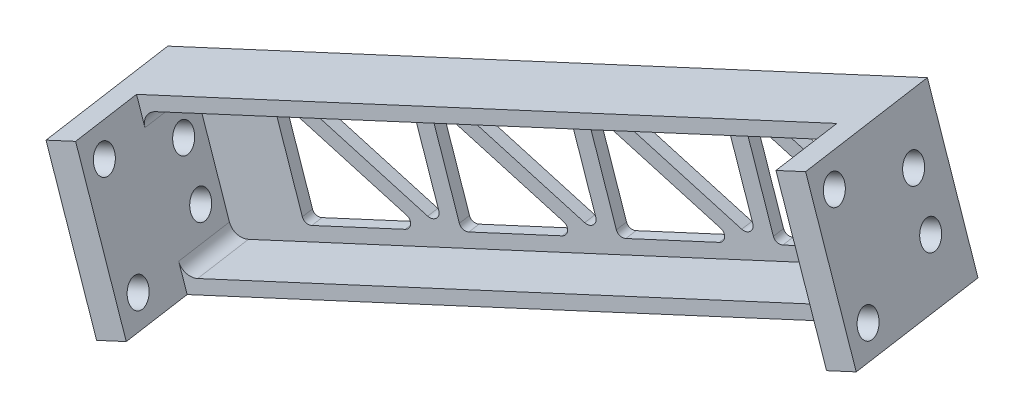
SolidWorks part; units mm, degrees
ref_plane "Front Plane" through (0, 0, 0) normal (0, 0, 1) x (1, 0, 0)
ref_plane "Top Plane" through (0, 0, 0) normal (0, 1, 0) x (1, 0, 0)
ref_plane "Right Plane" through (0, 0, 0) normal (1, 0, 0) x (0, 0, -1)
sketch3d "3DSketch1"
  line L0 (0, 0, 0) -> (-222.8841, -76.2, 50.8) construction
  line L1 (0, 0, 0) -> (-222.8841, 0, 50.8) construction
  line L2 (-222.8841, 0, 50.8) -> (-222.8841, -76.2, 50.8) construction
  line L3 (-222.8841, -76.2, 50.8) -> (-222.8841, -76.2, 0) construction
  line L4 (0, 0, 0) -> (-222.8841, -76.2, 0) construction
  line L5 (-193.5165, -66.1598, 44.1065) -> (-150.59, -51.484, 34.3226)
  line L6 (-150.59, -51.484, 34.3226) -> (0, 0, 0)
  line L7 (-193.5165, -66.1598, 44.1065) -> (-222.8841, -76.2, 50.8)
  dimension "D1" = 228.6
  dimension "D2" = 76.2
  dimension "D3" = 50.8
  dimension "D4" = 31.75
ref_plane "Plane1" through (0, 0, 0) normal (-0.925, -0.3162, 0.2108) x (0.1995, 0.0682, 0.9775)
ref_plane "Plane2" through (-222.8841, -76.2, 50.8) normal (-0.925, -0.3162, 0.2108) x (0.1995, 0.0682, 0.9775)
sketch "Sketch2" plane through (0, 0, 0) normal (-0.925, -0.3162, 0.2108) x (0.1995, 0.0682, 0.9775)
  line L1 (19.05, -19.05) -> (-19.05, -19.05)
  line L2 (19.05, -19.05) -> (19.05, 19.05)
  line L3 (19.05, 19.05) -> (-19.05, 19.05)
  line L4 (-19.05, -19.05) -> (-19.05, 19.05)
  line L5 (19.05, -19.05) -> (-19.05, 19.05) construction
  line L6 (19.05, 19.05) -> (-19.05, -19.05) construction
  point P0 (0, 0)
  dimension "D1" = 38.1
extrude "Boss-Extrude1" add sketch "Sketch2" along normal blind 6.35
sketch "Sketch3" plane through (-5.8735, -2.008, 1.3387) normal (-0.925, -0.3162, 0.2108) x (0.1995, 0.0682, 0.9775)
  line L0 (-15.875, -15.875) -> (0, -15.875)
  line L1 (-19.05, 19.05) -> (0, 19.05)
  line L2 (-19.05, 19.05) -> (-19.05, -19.05)
  line L3 (-19.05, -19.05) -> (0, -19.05)
  line L4 (0, 19.05) -> (0, 15.875)
  line L5 (-19.05, 19.05) -> (0, -19.05) construction
  line L6 (-19.05, -19.05) -> (0, 19.05) construction
  line L7 (-15.875, 15.875) -> (-15.875, -15.875)
  line L8 (-15.875, 15.875) -> (0, 15.875)
  line L9 (0, -15.875) -> (0, -19.05)
  line L10 (-19.05, 19.05) -> (-19.05, -19.05) construction
  line L11 (19.05, 19.05) -> (-19.05, 19.05) construction
  point P0 (-9.525, 0)
  dimension "D1" = 38.1
  dimension "D2" = 19.05
  dimension "D3" = 3.175
extrude "Boss-Extrude2" add sketch "Sketch3" along normal up to vertex (156.4566 mm away) up to point (-150.59, -51.484, 34.3226)
sketch "Sketch4" plane through (-150.59, -51.484, 34.3226) normal (-0.925, -0.3162, 0.2108) x (0.1995, 0.0682, 0.9775)
  line L1 (-19.05, 19.05) -> (19.05, 19.05)
  line L2 (-19.05, 19.05) -> (-19.05, -19.05)
  line L3 (-19.05, -19.05) -> (19.05, -19.05)
  line L4 (19.05, 19.05) -> (19.05, -19.05)
  line L5 (-19.05, 19.05) -> (19.05, -19.05) construction
  line L6 (-19.05, -19.05) -> (19.05, 19.05) construction
  point P0 (0, 0)
  dimension "D1" = 38.1
extrude "Boss-Extrude3" add sketch "Sketch4" against normal blind 6.35
fillet "Fillet1" radius 3.175 4 edges at (-12.5924, 12.472, -6.4204) (-2.3214, -17.5708, -6.4204) (-151.4354, -34.9959, 25.2248) (-141.1643, -65.0386, 25.2248)
hole_wizard "1/4 (0.25) Diameter Hole1" positions "Sketch6" profile "Sketch7" hole size "1/4" standard "ANSI Inch" end condition up to next
sketch "Sketch6" plane through (-144.7165, -49.4759, 32.9839) normal (0.925, 0.3162, -0.2108) x (-0.1995, -0.0682, -0.9775)
  line L0 (0, -19.05) -> (-19.05, -19.05) construction
  line L1 (-19.05, -19.05) -> (-19.05, 19.05) construction
  line L2 (-19.05, 19.05) -> (0, 19.05) construction
  line L3 (15.875, -12.7) -> (15.875, 12.7) construction
  point P0 (9.525, -6.35)
  point P2 (-12.7, -12.7)
  point P4 (-12.7, 12.7)
  point P6 (9.4701, 6.35)
  dimension "D1" = 6.35
  dimension "D2" = 6.35
  dimension "D3" = 6.35
  dimension "D4" = 12.7
  dimension "D5" = 12.7
  dimension "D6" = 6.35
sketch "Sketch7" plane through (-144.5623, -56.1341, 23.673) normal (-0.0803, 0.7048, 0.7048) x (-0.3715, 0.635, -0.6773)
  line L0 (0, 0) -> (0, 25.6035)
  line L1 (0, 25.6035) -> (3.175, 25.6035)
  line L2 (3.175, 25.6035) -> (3.175, 0)
  line L5 (3.175, 0) -> (0, 0)
  line L11 (0, -6.35) -> (0, 107.95) construction
  dimension "Thru Hole Dia." = 6.35
  dimension "Thru Hole Depth" = 25.6035
sketch "Sketch8" plane through (-144.7165, -49.4759, 32.9839) normal (0.925, 0.3162, -0.2108) x (-0.1995, -0.0682, -0.9775)
  circle A0 centre (9.4701, 6.35) radius 5.334 construction
  circle A1 centre (9.525, -6.35) radius 5.334 construction
  circle A2 centre (-12.7, -12.7) radius 5.334 construction
  circle A3 centre (-12.7, 12.7) radius 5.334 construction
  dimension "D1" = 10.668
ref_plane "Plane3" through (-75.295, -25.742, 17.1613) normal (0.925, 0.3162, -0.2108) x (-0.1995, -0.0682, -0.9775)
mirror "Mirror1" about plane through (-75.295, -25.742, 17.1613) normal (0.925, 0.3162, -0.2108) of "1/4 (0.25) Diameter Hole1"
sketch "Sketch9" plane through (-3.1668, -1.0827, -15.5182) normal (0.1995, 0.0682, 0.9775) x (0.9799, -0.0139, -0.199)
  line L0 (-6.0635, -11.5148) -> (-12.6596, 7.3449)
  line L1 (-14.6822, 8.3194) -> (-33.5419, 1.7233)
  line L2 (-33.7068, -1.2054) -> (-8.251, -13.4691)
  line L3 (-149.9286, -35.6184) -> (-14.2318, 11.8404) construction
  line L4 (6.289, -17.9819) -> (-6.289, 17.9819) construction
  line L5 (-149.9286, -35.6184) -> (-14.2318, 11.8404) construction
  line L6 (0.2951, -20.0783) -> (-12.283, 15.8856) construction
  line L7 (-37.9452, -2.6877) -> (-12.4894, -14.9514)
  line L8 (-12.6544, -17.8801) -> (-31.5141, -24.4761)
  line L9 (-33.5367, -23.5017) -> (-40.1327, -4.642)
  line L10 (-139.4469, -65.5884) -> (-3.7501, -18.1295) construction
  line L11 (-8.6204, -4.2041) -> (-36.8347, -14.0719) construction
  arc A0 (-33.5419, 1.7233) -> (-33.7068, -1.2054) centre (-33.0178, 0.2248) ccw
  arc A1 (-12.6596, 7.3449) -> (-14.6822, 8.3194) centre (-14.1581, 6.8209) ccw
  arc A2 (-6.0635, -11.5148) -> (-8.251, -13.4691) centre (-7.562, -12.0389) cw
  arc A3 (-37.9452, -2.6877) -> (-40.1327, -4.642) centre (-38.6342, -4.1179) ccw
  arc A4 (-31.5141, -24.4761) -> (-33.5367, -23.5017) centre (-32.0382, -22.9776) cw
  arc A5 (-12.6544, -17.8801) -> (-12.4894, -14.9514) centre (-13.1784, -16.3816) ccw
  point P13 (-37.1596, 0.4581)
  point P16 (-13.1837, 8.8434)
  point P19 (-4.7983, -15.1325)
  point P29 (-33.0126, -25.0002)
  point P32 (-9.0367, -16.6148)
  dimension "D5" = 1.5875
  dimension "D9" = 1.5875
  dimension "D1" = 25.4
  dimension "D2" = 25.4
  dimension "D3" = 3.175
  dimension "D4" = 3.175
  dimension "D6" = 3.175
  dimension "D7" = 3.175
  dimension "D8" = 25.4
extrude "Cut-Extrude1" cut sketch "Sketch9" against normal up to next
pattern_linear "LPattern1" count 4 spacing 33.655 along (-0.925, -0.3162, 0.2108) of "Cut-Extrude1"
